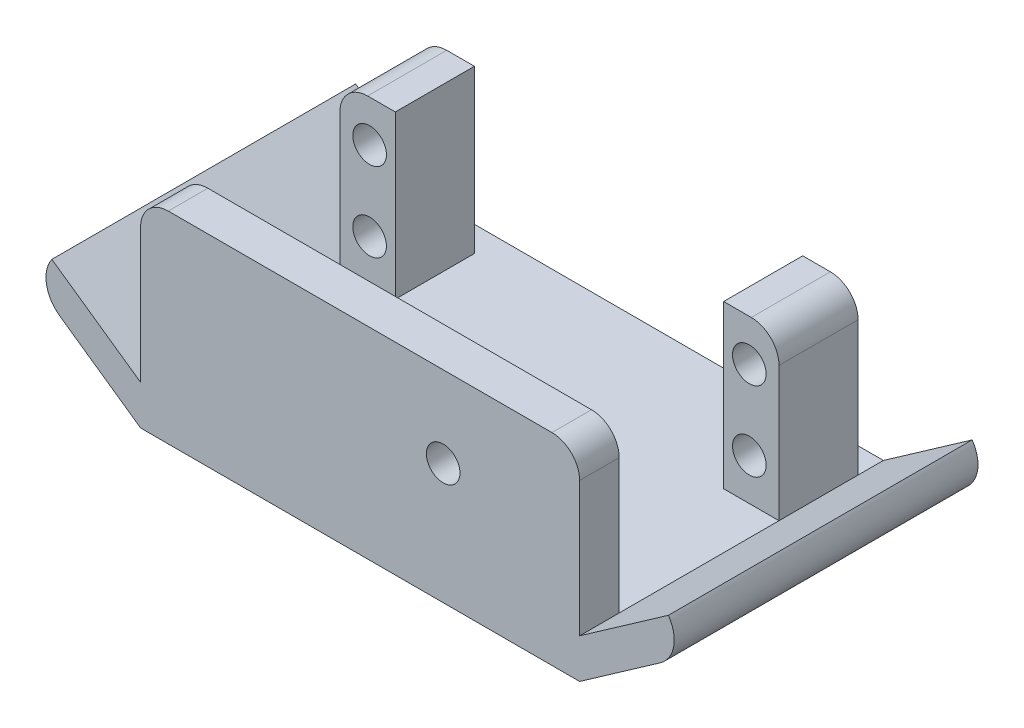
SolidWorks part; units mm, degrees
ref_plane "Front" through (0, 0, 0) normal (0, 0, 1) x (1, 0, 0)
ref_plane "Top" through (0, 0, 0) normal (0, 1, 0) x (1, 0, 0)
ref_plane "Right" through (0, 0, 0) normal (1, 0, 0) x (0, 0, -1)
sketch "Sketch1" plane through (0, 0, 0) normal (0, 1, 0) x (1, 0, 0)
  line L1 (0, 0) -> (55.5, 0)
  line L2 (0, 0) -> (0, 38.4)
  line L3 (0, 38.4) -> (55.5, 38.4)
  line L4 (55.5, 0) -> (55.5, 38.4)
  dimension "D1" = 55.5
  dimension "D2" = 38.4
extrude "base" add sketch "Sketch1" along normal blind 5
sketch "Sketch2" plane through (0, 0, -38.4) normal (0, 0, -1) x (-1, 0, 0)
  line L1 (0, 5) -> (0, 0) construction
  line L2 (-55.5, 0) -> (0, 0)
  line L3 (-55.5, 0) -> (-55.5, 25.5)
  line L4 (-55.5, 25.5) -> (0, 25.5)
  line L5 (0, 0) -> (0, 25.5)
  line L6 (-55.5, 5) -> (0, 5) construction
  dimension "D1" = 20.5
extrude "wall" add sketch "Sketch2" against normal blind 5
ref_plane "Plane1" through (0, 0, -8.2) normal (0, 0, 1) x (1, 0, 0)
sketch "Sketch3" plane through (0, 0, -8.2) normal (0, 0, 1) x (1, 0, 0)
  line L0 (0, 5) -> (55.5, 5) construction
  line L1 (0, 25.5) -> (7, 25.5)
  line L2 (0, 25.5) -> (0, 5)
  line L3 (0, 5) -> (7, 5)
  line L4 (7, 25.5) -> (7, 5)
  line L5 (27.75, 5) -> (27.75, 25.5) construction
  line L6 (55.5, 5) -> (0, 5) construction
  line L7 (0, 25.5) -> (55.5, 25.5) construction
  line L8 (55.5, 5) -> (48.5, 5)
  line L9 (48.5, 25.5) -> (48.5, 5)
  line L10 (55.5, 25.5) -> (48.5, 25.5)
  line L11 (55.5, 25.5) -> (55.5, 5)
  dimension "D1" = 7
extrude "mountingTabs" add sketch "Sketch3" along normal blind 5
sketch "Sketch4" plane through (0, 0, 0) normal (0, 0, 1) x (1, 0, 0)
  line L0 (27.75, 0) -> (27.75, 25.5) construction
  line L1 (0, 0) -> (55.5, 0) construction
  line L2 (0, 25.5) -> (55.5, 25.5) construction
  line L3 (0, 0) -> (-10.2089, 7.1483)
  line L4 (0, 5) -> (-11.2182, 12.8551)
  line L5 (0, 5) -> (0, 0)
  line L6 (55.5, 5) -> (66.7182, 12.8551)
  line L7 (55.5, 5) -> (55.5, 0)
  line L8 (55.5, 0) -> (65.7089, 7.1483)
  arc A0 (-11.2182, 12.8551) -> (-10.2089, 7.1483) centre (-7.8572, 10.5069) ccw
  arc A1 (66.7182, 12.8551) -> (65.7089, 7.1483) centre (63.3572, 10.5069) cw
  dimension "D1" = 145
  dimension "D2" = 12.4627
  dimension "D3" = 13.6949
extrude "lips" add sketch "Sketch4" against normal up to surface (38.4 mm away) up to face at (27.75, 12.75, -38.4)
sketch "Sketch5" plane through (0, 0, -3.2) normal (0, 0, 1) x (1, 0, 0)
  line L0 (27.75, 0) -> (27.75, 25.5) construction
  line L3 (0, 15.25) -> (55.5, 15.25) construction
  line L4 (0, 25.5) -> (0, 5) construction
  line L5 (55.5, 5) -> (55.5, 25.5) construction
  line L6 (7, 25.5) -> (0, 25.5) construction
  line L7 (0, 0) -> (55.5, 0) construction
  line L8 (0, 25.5) -> (55.5, 25.5) construction
  circle A0 centre (3.75, 20.25) radius 2.125
  circle A1 centre (3.75, 10.25) radius 2.125
  circle A4 centre (51.75, 10.25) radius 2.125
  circle A5 centre (51.75, 20.25) radius 2.125
  dimension "D1" = 4.25
  dimension "D2" = 5.25
  dimension "D3" = 3.75
extrude "mountingHoles" cut sketch "Sketch5" against normal blind 5
fillet "fillets" radius 3.5 4 edges at (55.5, 25.5, -35.9) (55.5, 25.5, -5.7) (0, 25.5, -35.9) (0, 25.5, -5.7)
sketch "Sketch6" plane through (0, 0, -33.4) normal (0, 0, 1) x (1, 0, 0)
  line L0 (3.5, 25.5) -> (52, 25.5) construction
  line L1 (55.5, 5) -> (55.5, 22) construction
  circle A0 centre (38.25, 15.25) radius 2.125
  dimension "D1" = 4.25
  dimension "D2" = 10.25
  dimension "D3" = 17.25
extrude "throughHole" cut sketch "Sketch6" against normal blind 5
ref_plane "Plane2" through (0, 0, 0) normal (0, 0, 1) x (1, 0, 0)
mirror "Mirror3" about plane through (0, 0, 0) normal (0, 0, 1) of "fillets", "throughHole", "mountingHoles", "lips", "mountingTabs", "wall", "base"
sketch "Sketch7" plane through (0, 0, 0) normal (0, 0, 1) x (1, 0, 0)
  line L1 (-26.7687, 48.7867) -> (77.7481, 48.7867)
  line L2 (-26.7687, 48.7867) -> (-26.7687, -17.5413)
  line L3 (-26.7687, -17.5413) -> (77.7481, -17.5413)
  line L4 (77.7481, 48.7867) -> (77.7481, -17.5413)
extrude "Cut-Extrude1" cut sketch "Sketch7" against normal blind 73
sketch "Sketch8" plane through (0, 0, 8.2) normal (0, 0, 1) x (1, 0, 0)
  line L4 (7, 25.5) -> (3.5, 25.5)
  line L5 (0, 22) -> (0, 5)
  line L6 (0, 5) -> (7, 5)
  line L7 (7, 5) -> (7, 25.5)
  line L8 (7, 25.5) -> (3.5, 25.5)
  line L9 (0, 22) -> (0, 5)
  line L10 (0, 5) -> (7, 5)
  line L11 (7, 5) -> (7, 25.5)
  line L12 (55.5, 5) -> (55.5, 22)
  line L13 (52, 25.5) -> (48.5, 25.5)
  line L14 (48.5, 25.5) -> (48.5, 5)
  line L15 (48.5, 5) -> (55.5, 5)
  line L16 (55.5, 5) -> (55.5, 22)
  line L17 (52, 25.5) -> (48.5, 25.5)
  line L18 (48.5, 25.5) -> (48.5, 5)
  line L19 (48.5, 5) -> (55.5, 5)
  circle A0 centre (3.75, 20.25) radius 2.125 construction
  arc A1 (3.5, 25.5) -> (0, 22) centre (3.5, 22) ccw
  arc A2 (3.5, 25.5) -> (0, 22) centre (3.5, 22) ccw
  arc A3 (55.5, 22) -> (52, 25.5) centre (52, 22) ccw
  arc A4 (55.5, 22) -> (52, 25.5) centre (52, 22) ccw
  circle A5 centre (3.75, 20.25) radius 2.125
  circle A6 centre (3.75, 10.25) radius 2.125 construction
  circle A7 centre (3.75, 10.25) radius 2.125
  circle A8 centre (51.75, 20.25) radius 2.125 construction
  circle A9 centre (51.75, 20.25) radius 2.125
  circle A10 centre (51.75, 10.25) radius 2.125 construction
  circle A11 centre (51.75, 10.25) radius 2.125
  dimension "D1" = 0
  dimension "D2" = 0
extrude "Boss-Extrude1" add sketch "Sketch8" along normal blind 5
